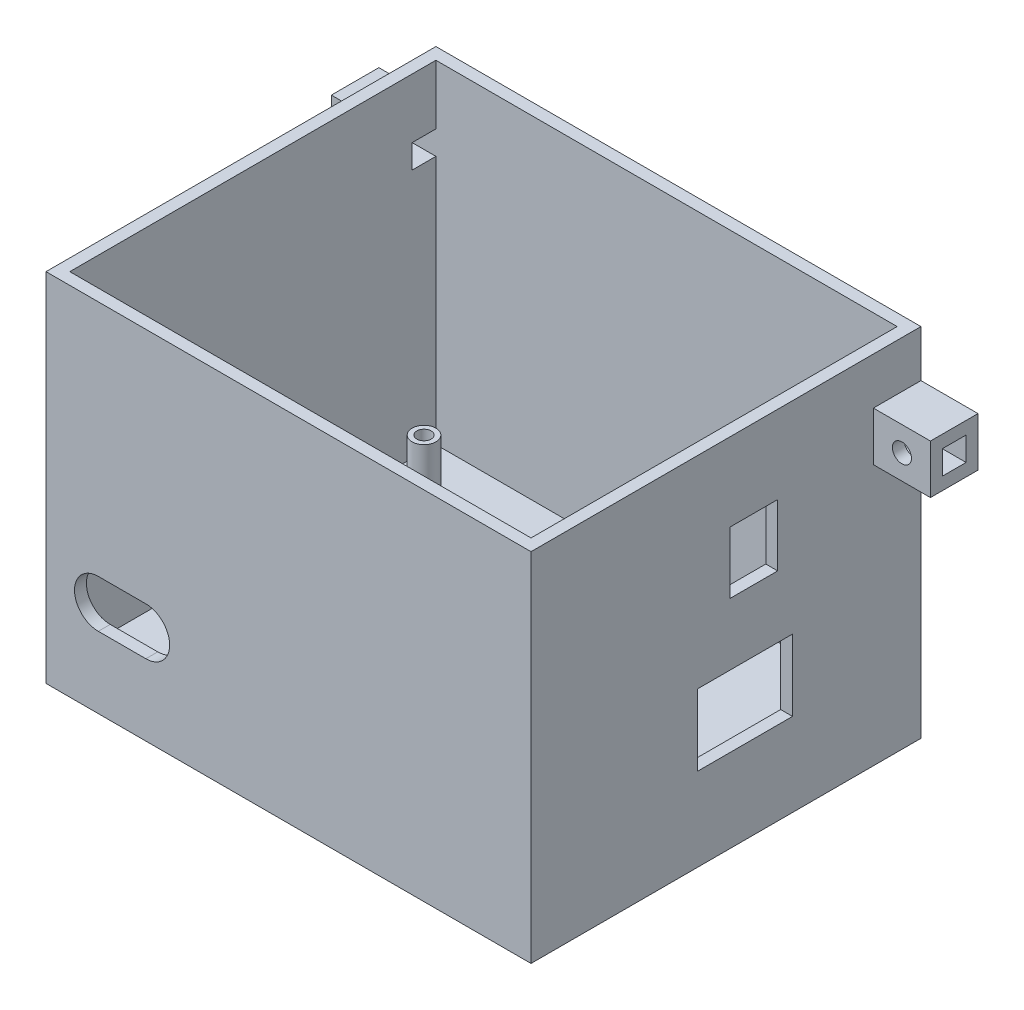
SolidWorks part; units mm, degrees
ref_plane "Front" through (0, 0, 0) normal (0, 0, 1) x (1, 0, 0)
ref_plane "Top" through (0, 0, 0) normal (0, 1, 0) x (1, 0, 0)
ref_plane "Right" through (0, 0, 0) normal (1, 0, 0) x (0, 0, -1)
sketch "Sketch1" plane through (0, 0, 0) normal (0, 1, 0) x (1, 0, 0)
  line L1 (-51, -41) -> (51, -41)
  line L2 (-51, -41) -> (-51, 41)
  line L3 (-51, 41) -> (51, 41)
  line L4 (51, -41) -> (51, 41)
  line L5 (-51, -41) -> (51, 41) construction
  line L6 (-51, 41) -> (51, -41) construction
  point P0 (0, 0)
  dimension "D1" = 102
  dimension "D2" = 82
extrude "Boss-Extrude1" add sketch "Sketch1" along normal blind 5
sketch "Sketch2" plane through (0, 5, 0) normal (0, 1, 0) x (1, 0, 0)
  line L1 (-48.5, -38.5) -> (48.5, -38.5)
  line L2 (-48.5, -38.5) -> (-48.5, 38.5)
  line L3 (-48.5, 38.5) -> (48.5, 38.5)
  line L4 (48.5, -38.5) -> (48.5, 38.5)
  line L5 (-48.5, -38.5) -> (48.5, 38.5) construction
  line L6 (-48.5, 38.5) -> (48.5, -38.5) construction
  line L7 (-51, -41) -> (51, -41)
  line L8 (-51, -41) -> (-51, 41)
  line L9 (-51, 41) -> (51, 41)
  line L10 (51, -41) -> (51, 41)
  line L11 (-51, -41) -> (51, 41) construction
  line L12 (-51, 41) -> (51, -41) construction
  point P0 (0, 0)
  point P6 (0, 0)
extrude "Boss-Extrude2" add sketch "Sketch2" along normal blind 70
sketch "Sketch4" plane through (0, 0, 41) normal (0, 0, 1) x (1, 0, 0)
  line L0 (-40, 20) -> (-30, 20) construction
  line L1 (-40, 25) -> (-30, 25)
  line L2 (-40, 15) -> (-30, 15)
  line L3 (-51, 75) -> (-51, 0) construction
  line L4 (-51, 0) -> (51, 0) construction
  arc A0 (-40, 25) -> (-40, 15) centre (-40, 20) ccw
  arc A1 (-30, 15) -> (-30, 25) centre (-30, 20) ccw
  point P2 (-35, 20)
  dimension "D1" = 10
  dimension "D2" = 10
  dimension "D3" = 16
  dimension "D4" = 20
extrude "Cut-Extrude1" cut sketch "Sketch4" against normal blind 3
sketch "Sketch5" plane through (0, 0, -41) normal (0, 0, -1) x (-1, 0, 0)
  line L0 (51, 54.848) -> (63, 54.848)
  line L1 (-63, 54.848) -> (-51, 54.848)
  line L2 (-63, 54.848) -> (-63, 65.152)
  line L3 (-63, 65.152) -> (-51, 65.152)
  line L4 (-51, 54.848) -> (-51, 65.152)
  line L5 (-63, 54.848) -> (-51, 65.152) construction
  line L6 (-63, 65.152) -> (-51, 54.848) construction
  line L7 (-51, 0) -> (51, 0) construction
  line L8 (51, 54.848) -> (51, 65.152)
  line L9 (51, 65.152) -> (63, 65.152)
  line L10 (63, 54.848) -> (63, 65.152)
  line L11 (51, 54.848) -> (63, 65.152) construction
  line L12 (51, 65.152) -> (63, 54.848) construction
  circle A0 centre (-57, 60) radius 2
  circle A1 centre (57, 60) radius 2
  point P0 (-57, 60)
  point P11 (57, 60)
  dimension "D4" = 4
  dimension "D1" = 60
  dimension "D2" = 57
  dimension "D3" = 12
  dimension "D6" = 10.3041
  dimension "D5" = 2
extrude "Boss-Extrude4" add sketch "Sketch5" against normal blind 10
sketch "Sketch9" plane through (51, 0, 0) normal (1, 0, 0) x (0, 0, -1)
  line L1 (-6, 17.5) -> (14, 17.5)
  line L2 (-6, 17.5) -> (-6, 32.5)
  line L3 (-6, 32.5) -> (14, 32.5)
  line L4 (14, 17.5) -> (14, 32.5)
  line L5 (-6, 17.5) -> (14, 32.5) construction
  line L6 (-6, 32.5) -> (14, 17.5) construction
  line L7 (-41, 0) -> (41, 0) construction
  line L8 (41, 75) -> (41, 65.152) construction
  line L11 (0.8752, 45.5604) -> (10.8752, 45.5604)
  line L12 (0.8752, 45.5604) -> (0.8752, 58.5604)
  line L13 (0.8752, 58.5604) -> (10.8752, 58.5604)
  line L14 (10.8752, 45.5604) -> (10.8752, 58.5604)
  point P0 (4, 25)
  dimension "D1" = 15
  dimension "D2" = 25
  dimension "D3" = 37
  dimension "D4" = 20
  dimension "D5" = 13
  dimension "D6" = 10
  dimension "D7" = 20.5604
extrude "Cut-Extrude7" cut sketch "Sketch9" against normal blind 10
sketch "Sketch10" plane through (0, 5, 0) normal (0, 1, 0) x (1, 0, 0)
  line L1 (-48.5, 38.5) -> (-48.5, -38.5) construction
  line L2 (48.5, 38.5) -> (-48.5, 38.5) construction
  circle A0 centre (16.5, -20) radius 2.5
  circle A1 centre (-41.5, -20) radius 2.5
  circle A2 centre (16.5, 29) radius 2.5
  circle A3 centre (-41.5, 29) radius 2.5
  dimension "D1" = 49
  dimension "D2" = 58
  dimension "D3" = 5
  dimension "D4" = 49
  dimension "D5" = 58
  dimension "D6" = 7
  dimension "D7" = 9.5
extrude "Boss-Extrude5" add sketch "Sketch10" along normal blind 10
sketch "Sketch11" plane through (0, 5, 0) normal (0, 1, 0) x (1, 0, 0)
  circle A0 centre (-41.5, 29) radius 1.5
  circle A1 centre (16.5, 29) radius 1.5
  circle A2 centre (-41.5, -20) radius 1.5
  circle A3 centre (16.5, -20) radius 1.5
  dimension "D1" = 3
  dimension "D2" = 3
  dimension "D3" = 3
  dimension "D4" = 3
extrude "Cut-Extrude8" cut sketch "Sketch11" along normal blind 10
sketch "Sketch12" plane through (51, 0, 0) normal (1, 0, 0) x (0, 0, -1)
  line L0 (41, 54.848) -> (41, 0) construction
  line L1 (33.5, 57.5) -> (38.5, 57.5)
  line L2 (33.5, 57.5) -> (33.5, 62.5)
  line L3 (33.5, 62.5) -> (38.5, 62.5)
  line L4 (38.5, 57.5) -> (38.5, 62.5)
  line L5 (33.5, 57.5) -> (38.5, 62.5) construction
  line L6 (33.5, 62.5) -> (38.5, 57.5) construction
  line L7 (-41, 75) -> (41, 75) construction
  point P0 (36, 60)
  dimension "D1" = 5
  dimension "D2" = 5
  dimension "D3" = 5
  dimension "D4" = 15
extrude "Cut-Extrude9" cut sketch "Sketch12" against normal through all both and the other way through all
